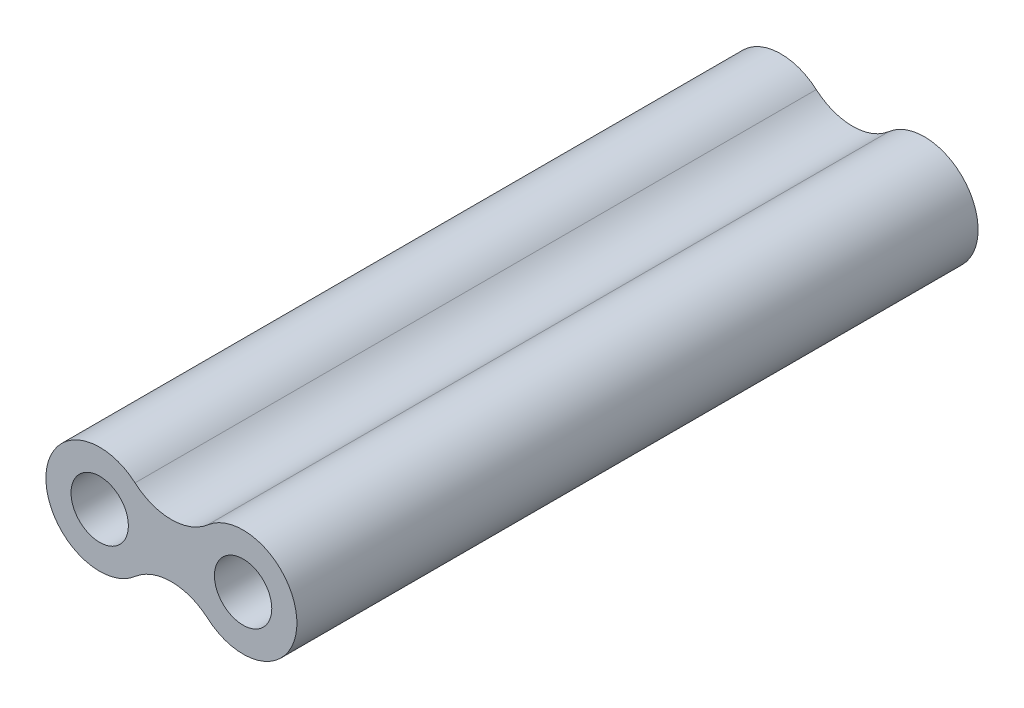
SolidWorks part; units mm, degrees
material "Rubber"
ref_plane "Front Plane" through (0, 0, 0) normal (0, 0, 1) x (1, 0, 0)
ref_plane "Top Plane" through (0, 0, 0) normal (0, 1, 0) x (1, 0, 0)
ref_plane "Right Plane" through (0, 0, 0) normal (1, 0, 0) x (0, 0, -1)
ref_axis "X" through (-88.99, 0, 0) along (1, 0, 0)
ref_axis "Y" through (0, 55, 0) along (0, -1, 0)
ref_axis "Z" through (0, 0, -88.99) along (0, 0, 1)
sketch "Sketch1" plane through (0, 0, 0) normal (0, 0, 1) x (1, 0, 0)
  circle A0 centre (0, 0) radius 1.5 construction
  circle A1 centre (0, 0) radius 3
  dimension "D1" = 3
  dimension "D2" = 6
extrude "Boss-Extrude1" add sketch "Sketch1" along normal mid plane 38
sketch "Sketch5" plane through (0, 0, 19) normal (0, 0, 1) x (1, 0, 0)
  point P0 (0, 0)
hole_wizard "M3 Clearance Hole" positions "Sketch5" profile "Sketch4" hole size "M3" standard "ANSI Metric" end condition through all
sketch "Sketch4" plane through (0, 0, 19) normal (1, 0, 0) x (0, -1, 0)
  line L0 (0, 0) -> (0, 38)
  line L1 (0, 38) -> (1.6, 38)
  line L2 (1.6, 38) -> (1.6, 0)
  line L5 (1.6, 0) -> (0, 0)
  line L11 (0, -6.35) -> (0, 107.95) construction
  dimension "Thru Hole Dia." = 3.2
  dimension "Thru Hole Depth" = 38
sketch "Sketch2" plane through (0, 0, 0) normal (0, 0, 1) x (1, 0, 0)
  line L0 (0, 0) -> (8, 0) construction
  line L1 (4, 1.5) -> (4, -1.5) construction
  circle A0 centre (8, 0) radius 1.5 construction
  circle A1 centre (8, 0) radius 3
  circle A3 centre (0, 0) radius 3 construction
  circle A4 centre (0, 0) radius 1.5 construction
  arc A5 (1.9726, 2.2603) -> (6.0274, 2.2603) centre (4, 4.5833) ccw
  arc A6 (1.9726, -2.2603) -> (6.0274, -2.2603) centre (4, -4.5833) cw
  circle A7 centre (0, 0) radius 3
  dimension "D1" = 3
  dimension "D2" = 8
extrude "Boss-Extrude2" add sketch "Sketch2" along normal up to surface and the other way up to surface contours A1 | A7 A6 A1 A5 region at (8, 0, 0) region at (4, 0, 0) up to face at (1.6, 0, 19) other way up to face at (1.6, 0, -19)
sketch "Sketch8" plane through (0, 0, 19) normal (0, 0, 1) x (1, 0, 0)
  point P0 (8, 0)
hole_wizard "M3 Clearance Hole2" positions "Sketch8" profile "Sketch7" hole size "M3" standard "ANSI Metric" end condition through all
sketch "Sketch7" plane through (8, 0, 19) normal (1, 0, 0) x (0, -1, 0)
  line L0 (0, 0) -> (0, 38)
  line L1 (0, 38) -> (1.6, 38)
  line L2 (1.6, 38) -> (1.6, 0)
  line L5 (1.6, 0) -> (0, 0)
  line L11 (0, -6.35) -> (0, 107.95) construction
  dimension "Thru Hole Dia." = 3.2
  dimension "Thru Hole Depth" = 38
equation "\"Spacing\"= 8mm"
equation "\"D2@Sketch2\"=\"Spacing\""
